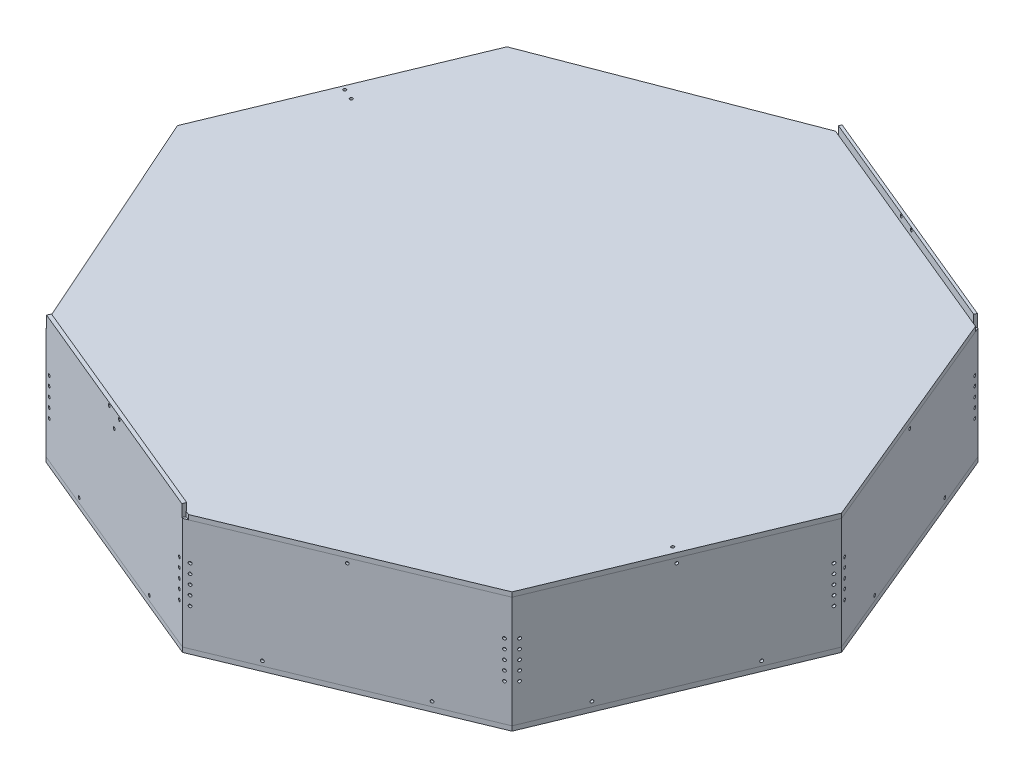
SolidWorks part; units mm, degrees
material "PMMA"
ref_plane "前视基准面" through (0, 0, 0) normal (0, 0, 1) x (1, 0, 0)
ref_plane "上视基准面" through (0, 0, 0) normal (0, 1, 0) x (1, 0, 0)
ref_plane "右视基准面" through (0, 0, 0) normal (1, 0, 0) x (0, 0, -1)
sketch "草图1" plane through (0, 0, 0) normal (0, 1, 0) x (1, 0, 0)
  line L0 (0, 0) -> (351.7775, 0) construction
  line L1 (351.7775, 0) -> (248.7442, 248.7442)
  line L2 (248.7442, 248.7442) -> (0, 351.7775)
  line L3 (0, 351.7775) -> (-248.7442, 248.7442)
  line L4 (-248.7442, 248.7442) -> (-351.7775, 0)
  line L5 (-351.7775, 0) -> (-248.7442, -248.7442)
  line L6 (-248.7442, -248.7442) -> (0, -351.7775)
  line L7 (0, -351.7775) -> (248.7442, -248.7442)
  line L8 (248.7442, -248.7442) -> (351.7775, 0)
  line L9 (0, -355.0246) -> (251.0403, -251.0403)
  line L10 (251.0403, -251.0403) -> (355.0246, 0)
  line L11 (355.0246, 0) -> (251.0403, 251.0403)
  line L12 (251.0403, 251.0403) -> (0, 355.0246)
  line L13 (0, 355.0246) -> (-251.0403, 251.0403)
  line L14 (-251.0403, 251.0403) -> (-355.0246, 0)
  line L15 (-355.0246, 0) -> (-251.0403, -251.0403)
  line L16 (-251.0403, -251.0403) -> (0, -355.0246)
  circle A2 centre (0, 0) radius 325 construction
  dimension "D1" = 3
  dimension "D3" = 650
extrude "凸台-拉伸1" add sketch "草图1" along normal blind 120
sketch "草图2" plane through (0, 0, 0) normal (0, -1, 0) x (1, 0, 0)
  line L10 (0, 355.0246) -> (-251.0403, 251.0403)
  line L11 (-251.0403, 251.0403) -> (-355.0246, 0)
  line L12 (-355.0246, 0) -> (-251.0403, -251.0403)
  line L13 (-251.0403, -251.0403) -> (0, -355.0246)
  line L14 (0, -355.0246) -> (251.0403, -251.0403)
  line L15 (251.0403, -251.0403) -> (355.0246, 0)
  line L16 (355.0246, 0) -> (251.0403, 251.0403)
  line L17 (251.0403, 251.0403) -> (0, 355.0246)
  line L18 (0, 355.0246) -> (-251.0403, 251.0403)
  line L19 (-251.0403, 251.0403) -> (-355.0246, 0)
  line L20 (-355.0246, 0) -> (-251.0403, -251.0403)
  line L21 (-251.0403, -251.0403) -> (0, -355.0246)
  line L22 (0, -355.0246) -> (251.0403, -251.0403)
  line L23 (251.0403, -251.0403) -> (355.0246, 0)
  line L24 (355.0246, 0) -> (251.0403, 251.0403)
  line L25 (251.0403, 251.0403) -> (0, 355.0246)
  dimension "D1" = 0
extrude "凸台-拉伸2" add sketch "草图2" along normal blind 5 separate body
sketch "草图3" plane through (0, -5, 0) normal (0, -1, 0) x (1, 0, 0)
  circle A0 centre (0, 0) radius 315 construction
  circle A1 centre (0, -315) radius 5.2
  circle A2 centre (-222.7386, -222.7386) radius 5.2
  circle A3 centre (-315, 0) radius 5.2
  circle A4 centre (-222.7386, 222.7386) radius 5.2
  circle A5 centre (0, 315) radius 5.2
  circle A6 centre (222.7386, 222.7386) radius 5.2
  circle A7 centre (315, 0) radius 5.2
  circle A8 centre (222.7386, -222.7386) radius 5.2
  circle A10 centre (0, 0) radius 22.5
  circle A11 centre (0, 0) radius 29 construction
  circle A12 centre (29, 0) radius 2.05
  circle A13 centre (-14.5, -25.1147) radius 2.05
  circle A14 centre (-14.5, 25.1147) radius 2.05
  dimension "D1" = 630
  dimension "D2" = 10.4
  dimension "D4" = 45
  dimension "D5" = 58
  dimension "D6" = 4.1
  dimension "D3" = 8
  dimension "D7" = 3
extrude "切除-拉伸1" cut sketch "草图3" against normal through all
sketch "草图6" plane through (0, -5, 0) normal (0, -1, 0) x (1, 0, 0)
  line L0 (0, 351.7775) -> (248.7442, 248.7442) construction
  line L1 (0, 351.7775) -> (248.7442, 248.7442) construction
  line L2 (124.3721, 300.2608) -> (0, 0) construction
  line L3 (-57.7871, 322.4293) -> (0, 0) construction
  line L4 (0, 0) -> (-187.1303, 268.8536) construction
  line L5 (-187.1303, 268.8536) -> (-57.7871, 322.4293) construction
  line L6 (-122.4587, 295.6415) -> (0, 0) construction
  line L7 (57.7871, 322.4293) -> (187.1303, 268.8536) construction
  line L8 (122.4587, 295.6415) -> (0, 0) construction
  circle A11 centre (57.7871, 322.4293) radius 1.6
  circle A12 centre (187.1303, 268.8536) radius 1.6
  circle A13 centre (268.8536, 187.1303) radius 1.6
  circle A14 centre (322.4293, 57.7871) radius 1.6
  circle A15 centre (322.4293, -57.7871) radius 1.6
  circle A16 centre (268.8536, -187.1303) radius 1.6
  circle A17 centre (187.1303, -268.8536) radius 1.6
  circle A18 centre (57.7871, -322.4293) radius 1.6
  circle A19 centre (-57.7871, -322.4293) radius 1.6
  circle A20 centre (-187.1303, -268.8536) radius 1.6
  circle A21 centre (-268.8536, -187.1303) radius 1.6
  circle A22 centre (-322.4293, -57.7871) radius 1.6
  circle A23 centre (-322.4293, 57.7871) radius 1.6
  circle A24 centre (-268.8536, 187.1303) radius 1.6
  circle A25 centre (-187.1303, 268.8536) radius 1.6
  circle A26 centre (-57.7871, 322.4293) radius 1.6
  dimension "D1" = 3.2
  dimension "D2" = 70
  dimension "D3" = 5
  dimension "D4" = 320
extrude "切除-拉伸2" cut sketch "草图6" against normal through all
sketch "草图4" plane through (0, 120, 0) normal (0, 1, 0) x (1, 0, 0)
  line L0 (-248.7442, -248.7442) -> (0, -351.7775) construction
  line L1 (248.7442, 248.7442) -> (0, 351.7775) construction
  line L2 (-248.7442, -248.7442) -> (0, -351.7775) construction
  line L3 (248.7442, 248.7442) -> (0, 351.7775) construction
  line L4 (4.573, -353.1305) -> (-252.9345, -246.4674)
  line L5 (252.9345, 246.4674) -> (-4.573, 353.1305)
  line L6 (303.0325, -125.5202) -> (-303.0325, 125.5202) construction
  line L7 (0, 0) -> (-18.7005, -45.1469) construction
  line L8 (-251.0403, -251.0403) -> (0, -355.0246)
  line L9 (0, -355.0246) -> (251.0403, -251.0403)
  line L10 (251.0403, -251.0403) -> (355.0246, 0)
  line L11 (355.0246, 0) -> (251.0403, 251.0403)
  line L12 (251.0403, 251.0403) -> (0, 355.0246)
  line L13 (0, 355.0246) -> (-251.0403, 251.0403)
  line L14 (-251.0403, 251.0403) -> (-355.0246, 0)
  line L15 (-355.0246, 0) -> (-251.0403, -251.0403)
  line L17 (4.573, -353.1305) -> (251.0403, -251.0403)
  line L18 (251.0403, -251.0403) -> (355.0246, 0)
  line L19 (355.0246, 0) -> (252.9345, 246.4674)
  line L21 (-4.573, 353.1305) -> (-251.0403, 251.0403) construction
  line L22 (-251.0403, 251.0403) -> (-355.0246, 0) construction
  line L23 (-355.0246, 0) -> (-252.9345, -246.4674) construction
  line L24 (-248.7442, 248.7442) -> (-351.7775, 0) construction
  line L25 (-251.0403, 251.0403) -> (-260.2791, 254.8672) construction
  line L26 (-260.2791, 254.8672) -> (-364.2634, 3.8268)
  line L27 (-364.2634, 3.8268) -> (-355.0246, 0) construction
  line L28 (-4.573, 353.1305) -> (-260.2791, 254.8672)
  line L29 (-364.2634, 3.8268) -> (-252.9345, -246.4674)
  circle A0 centre (295.6415, -122.4587) radius 1.6
  circle A1 centre (-295.6415, 122.4587) radius 1.6
  circle A2 centre (-307.6519, 127.4336) radius 1.6
  dimension "D4" = 3.2
  dimension "D2" = 0.5
  dimension "D3" = 0.5
  dimension "D5" = 5
  dimension "D6" = 10
  dimension "D7" = 5
  dimension "D1" = 0
extrude "凸台-拉伸3" add sketch "草图4" along normal blind 5 separate body
sketch "草图8" plane through (-125.5202, 0, 303.0325) normal (-0.3827, 0, 0.9239) x (0.9239, 0, 0.3827)
  line L1 (-134.6194, 120) -> (134.6194, 120)
  line L2 (-134.6194, 120) -> (-134.6194, 133)
  line L3 (-134.6194, 133) -> (134.6194, 133)
  line L4 (134.6194, 120) -> (134.6194, 133)
  line L5 (0, 133) -> (0, 120) construction
  line L6 (-10, 130) -> (10, 130) construction
  circle A1 centre (-10, 130) radius 1.6
  circle A2 centre (10, 130) radius 1.6
  dimension "D2" = 3.2
  dimension "D1" = 13
  dimension "D3" = 20
  dimension "D4" = 3
extrude "凸台-拉伸4" add sketch "草图8" against normal blind 4
extrude "凸台-拉伸6" add sketch "草图8<2>" against normal up to surface (656 mm away) from surface up to face at (125.5202, 60, -303.0325) starting at face at (124.3721, 60, -300.2608)
sketch "草图8<2>" plane through (-125.5202, 0, 303.0325) normal (-0.3827, 0, 0.9239) x (0.9239, 0, 0.3827) same geometry as "草图8"
sketch "草图9" plane through (-303.0325, 0, -125.5202) normal (-0.9239, 0, -0.3827) x (-0.3827, 0, 0.9239)
  line L0 (-70, 5) -> (70, 5) construction
  line L1 (0, 5) -> (0, 0) construction
  line L2 (135.862, 0) -> (-135.862, 0) construction
  line L3 (-135.862, 60) -> (135.862, 60) construction
  line L4 (-135.862, 120) -> (-135.862, 0) construction
  line L5 (135.862, 120) -> (135.862, 0) construction
  line L6 (-135.862, 120) -> (135.862, 120) construction
  line L7 (-129.6194, 80) -> (-129.6194, 40) construction
  line L8 (129.6194, 70) -> (129.6194, 50) construction
  circle A0 centre (-70, 5) radius 1.6
  circle A1 centre (70, 5) radius 1.6
  circle A4 centre (0, 115) radius 1.6
  circle A5 centre (-129.6194, 80) radius 1.6
  circle A6 centre (-129.6194, 40) radius 1.6
  circle A9 centre (129.6194, 70) radius 1.6
  circle A10 centre (129.6194, 50) radius 1.6
  circle A11 centre (-129.6194, 60) radius 1.6
  dimension "D2" = 3.2
  dimension "D4" = 3.2
  dimension "D6" = 3.2
  dimension "D1" = 5
  dimension "D3" = 140
  dimension "D5" = 40
  dimension "D7" = 5
  dimension "D8" = 5
  dimension "D9" = 5
  dimension "D10" = 20
extrude "切除-拉伸5" cut sketch "草图9" against normal through all both and the other way through all
pattern_circular "阵列(圆周)2" count 8 over 360 about axis through (0, 0, 0) along (0, -1, 0) of "切除-拉伸5"
sketch "草图10" plane through (0, 0, 0) normal (0, 1, 0) x (1, 0, 0)
  line L0 (248.7442, 248.7442) -> (238.7198, 252.8965)
  line L1 (248.7442, 248.7442) -> (0, 351.7775) construction
  line L2 (236.5403, 249.6345) -> (249.6345, 236.5403)
  line L3 (351.7775, 0) -> (248.7442, 248.7442) construction
  line L4 (252.8965, 238.7198) -> (248.7442, 248.7442)
  arc A0 (249.6345, 236.5403) -> (252.8965, 238.7198) centre (251.0487, 237.9545) ccw
  arc A1 (238.7198, 252.8965) -> (236.5403, 249.6345) centre (237.9545, 251.0487) ccw
  point P10 (256.7442, 229.4305)
  point P13 (229.4305, 256.7442)
  dimension "D2" = 2
  dimension "D1" = 8
extrude "凸台-拉伸5" add sketch "草图10" along normal blind 60 from offset 30 separate body
sketch "草图11" plane through (124.3721, 0, -300.2608) normal (0.3827, 0, -0.9239) x (-0.9239, 0, -0.3827)
  circle A10 centre (-129.6194, 80) radius 1.2
  circle A11 centre (-129.6194, 70) radius 1.2
  circle A12 centre (-129.6194, 60) radius 1.2
  circle A13 centre (-129.6194, 50) radius 1.2
  circle A14 centre (-129.6194, 40) radius 1.2
  dimension "D1" = 2.4
extrude "切除-拉伸6" cut sketch "草图11" against normal up to surface (6.091 mm away) up to face at (243.0874, 60, -243.0874)
sketch "草图13" plane through (300.2608, 0, -124.3721) normal (0.9239, 0, -0.3827) x (-0.3827, 0, -0.9239)
  circle A0 centre (129.6194, 80) radius 1.2
  circle A1 centre (129.6194, 70) radius 1.2
  circle A2 centre (129.6194, 60) radius 1.2
  circle A3 centre (129.6194, 50) radius 1.2
  circle A4 centre (129.6194, 40) radius 1.2
  dimension "D1" = 2.4
extrude "切除-拉伸7" cut sketch "草图13" against normal up to surface (7.0851 mm away) up to face at (240.6852, 80, -245.4895)
pattern_circular "阵列(圆周)3" count 8 over 360 about axis through (0, 0, 0) along (0, -1, 0) of bodies 122
sketch "草图14" plane through (0, -5, 0) normal (0, -1, 0) x (1, 0, 0)
  line L1 (50, -50) -> (-50, -50) construction
  line L2 (50, -50) -> (50, 50) construction
  line L3 (50, 50) -> (-50, 50) construction
  line L4 (-50, -50) -> (-50, 50) construction
  line L5 (50, -50) -> (-50, 50) construction
  line L6 (50, 50) -> (-50, -50) construction
  line L14 (54, -54) -> (54, 54) construction
  line L15 (54, 54) -> (-54, 54) construction
  line L16 (-54, -54) -> (-54, 54) construction
  line L17 (54, -54) -> (-54, -54) construction
  line L19 (-50, -50) -> (-54, -50)
  line L20 (-50, -50) -> (-50, 50)
  line L21 (-50, 50) -> (-54, 50)
  line L22 (-54, -50) -> (-54, 50)
  point P0 (0, 0)
  dimension "D1" = 100
  dimension "D2" = 4
extrude "凸台-拉伸7" add sketch "草图14" along normal blind 55 separate body
sketch "草图15" plane through (0, -60, 0) normal (0, -1, 0) x (1, 0, 0)
  line L0 (-50, 50) -> (-54, 50) construction
  line L1 (-50, -50) -> (50, -50)
  line L2 (-50, -50) -> (-50, 50)
  line L3 (-50, 50) -> (50, 50)
  line L4 (50, -50) -> (50, 50)
  line L5 (-50, -50) -> (-50, 50) construction
  line L6 (-54, -50) -> (-50, -50) construction
  dimension "D1" = 100
extrude "凸台-拉伸8" add sketch "草图15" along normal blind 3 separate body
sketch "草图16" plane through (0, -63, 0) normal (0, -1, 0) x (1, 0, 0)
  line L0 (50, 0) -> (-50, 0) construction
  line L1 (50, -50) -> (50, 50) construction
  line L2 (-50, 50) -> (-50, -50) construction
  circle A0 centre (0, 0) radius 3.05
  circle A1 centre (0, 0) radius 12.5 construction
  circle A2 centre (0, -12.5) radius 1.35
  circle A3 centre (-10.8253, 6.25) radius 1.35
  circle A4 centre (10.8253, 6.25) radius 1.35
  dimension "D1" = 6.1
  dimension "D2" = 25
  dimension "D3" = 2.7
  dimension "D4" = 3
extrude "切除-拉伸8" cut sketch "草图16" against normal up to next (3 mm away)
sketch "草图17" plane through (0, -5, 0) normal (0, -1, 0) x (1, 0, 0)
  line L0 (-59, -49.5402) -> (-59, 46.5588) construction
  line L1 (-50, -50) -> (-50, 50) construction
  line L2 (-50, 50) -> (-54, 50) construction
  line L3 (-54, -50) -> (-50, -50) construction
  line L4 (-54, 50) -> (-54, -50) construction
  circle A0 centre (-59, -30) radius 1.6
  circle A1 centre (-59, 30) radius 1.6
  circle A2 centre (-30, 59) radius 1.6
  circle A3 centre (30, 59) radius 1.6
  circle A4 centre (59, 30) radius 1.6
  circle A5 centre (59, -30) radius 1.6
  circle A6 centre (30, -59) radius 1.6
  circle A7 centre (-30, -59) radius 1.6
  circle A8 centre (0, 0) radius 66.1891 construction
  dimension "D2" = 3.2
  dimension "D1" = 5
  dimension "D3" = 20
  dimension "D4" = 20
  dimension "D5" = 4
extrude "切除-拉伸9" cut sketch "草图17" against normal up to next (5 mm away)
sketch "草图18" plane through (-54, 0, 0) normal (-1, 0, 0) x (0, 0, 1)
  line L0 (-50, -10) -> (50, -10) construction
  line L1 (-50, -60) -> (-50, -5) construction
  line L2 (50, -60) -> (50, -5) construction
  line L3 (50, -5) -> (-50, -5) construction
  line L4 (-50, -32.5) -> (-36.0118, -32.5) construction
  circle A0 centre (-30, -10) radius 1.6
  circle A1 centre (30, -10) radius 1.6
  circle A2 centre (30, -55) radius 1.6
  circle A3 centre (-30, -55) radius 1.6
  dimension "D1" = 3.2
  dimension "D2" = 5
  dimension "D3" = 20
  dimension "D4" = 20
extrude "切除-拉伸10" cut sketch "草图18" against normal up to next (4 mm away)
sketch "草图19" plane through (0, -63, 0) normal (0, -1, 0) x (1, 0, 0)
  line L0 (-45, -50) -> (-45, 50) construction
  line L1 (-50, -50) -> (50, -50) construction
  line L2 (50, 50) -> (-50, 50) construction
  line L3 (-50, 50) -> (-50, -50) construction
  circle A0 centre (-45, -30) radius 1.6
  circle A1 centre (-45, 30) radius 1.6
  dimension "D1" = 3.2
  dimension "D2" = 20
  dimension "D3" = 20
  dimension "D4" = 5
extrude "切除-拉伸11" cut sketch "草图19" against normal up to next (3 mm away)
